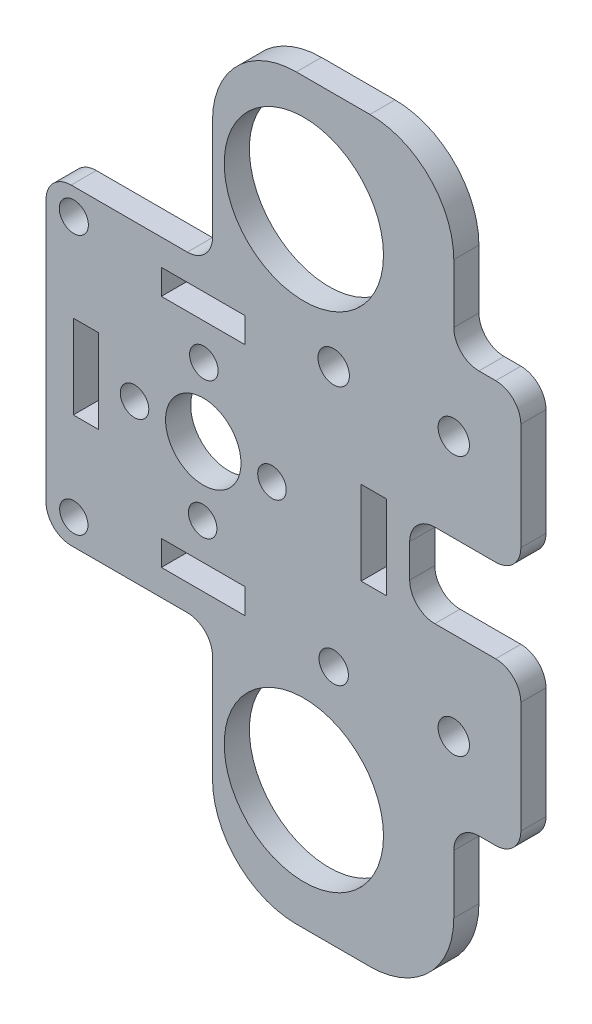
SolidWorks part; units mm, degrees
ref_plane "Front Plane" through (0, 0, 0) normal (0, 0, 1) x (1, 0, 0)
ref_plane "Top Plane" through (0, 0, 0) normal (0, 1, 0) x (1, 0, 0)
ref_plane "Right Plane" through (0, 0, 0) normal (1, 0, 0) x (0, 0, -1)
sketch "Sketch1" plane through (0, 0, 0) normal (0, 0, 1) x (1, 0, 0)
  line L0 (147.062, -92.9701) -> (147.062, -71.8565)
  line L1 (147.062, -92.9701) -> (127.2038, -92.9701)
  line L2 (127.2038, -92.9701) -> (127.2038, -111.5917)
  line L4 (147.062, -151.8871) -> (147.062, -155.8871)
  line L5 (145.9607, -111.5917) -> (157.9607, -111.5917) construction
  line L6 (157.9607, -111.5917) -> (157.9607, -81.5917) construction
  line L7 (157.9607, -111.5917) -> (157.9607, -141.5917) construction
  line L8 (147.062, -71.8565) -> (147.062, -67.8565)
  line L9 (127.2038, -111.5917) -> (127.2038, -130.2155)
  line L10 (127.2038, -130.2155) -> (147.062, -130.2155)
  line L11 (147.062, -130.2155) -> (147.062, -151.8871)
  line L13 (147.062, -67.8565) -> (175.8433, -67.8565)
  line L14 (147.062, -155.8871) -> (175.8433, -155.8871)
  line L15 (175.8433, -67.8565) -> (175.8433, -87.8565)
  line L16 (175.8433, -155.8871) -> (175.8433, -135.8871)
  line L17 (175.8433, -87.8565) -> (183.8433, -87.8565)
  line L18 (175.8433, -135.8871) -> (183.8433, -135.8871)
  line L19 (166.2936, -111.5917) -> (199.239, -111.5917) construction
  line L20 (145.9607, -111.5917) -> (131.9607, -111.5917) construction
  line L21 (145.9607, -111.5917) -> (145.9607, -97.5917) construction
  line L22 (145.9607, -111.5917) -> (145.9607, -125.5917) construction
  line L23 (157.9607, -111.5917) -> (166.2936, -111.5917) construction
  line L24 (130.4607, -106.5917) -> (133.4607, -106.5917)
  line L25 (130.4607, -106.5917) -> (130.4607, -116.5917)
  line L26 (130.4607, -116.5917) -> (133.4607, -116.5917)
  line L27 (133.4607, -106.5917) -> (133.4607, -116.5917)
  line L28 (130.4607, -106.5917) -> (133.4607, -116.5917) construction
  line L29 (130.4607, -116.5917) -> (133.4607, -106.5917) construction
  line L30 (140.9607, -99.0917) -> (150.9607, -99.0917)
  line L31 (140.9607, -99.0917) -> (140.9607, -96.0917)
  line L32 (140.9607, -96.0917) -> (150.9607, -96.0917)
  line L33 (150.9607, -99.0917) -> (150.9607, -96.0917)
  line L34 (140.9607, -99.0917) -> (150.9607, -96.0917) construction
  line L35 (140.9607, -96.0917) -> (150.9607, -99.0917) construction
  line L36 (140.9607, -127.0917) -> (150.9607, -127.0917)
  line L37 (140.9607, -127.0917) -> (140.9607, -124.0917)
  line L38 (140.9607, -124.0917) -> (150.9607, -124.0917)
  line L39 (150.9607, -127.0917) -> (150.9607, -124.0917)
  line L40 (140.9607, -127.0917) -> (150.9607, -124.0917) construction
  line L41 (140.9607, -124.0917) -> (150.9607, -127.0917) construction
  line L42 (185.7907, -111.5917) -> (185.7907, -106.5917) construction
  line L43 (164.7936, -106.5917) -> (167.7936, -106.5917)
  line L44 (164.7936, -106.5917) -> (164.7936, -116.5917)
  line L45 (164.7936, -116.5917) -> (167.7936, -116.5917)
  line L46 (167.7936, -106.5917) -> (167.7936, -116.5917)
  line L47 (164.7936, -106.5917) -> (167.7936, -116.5917) construction
  line L48 (164.7936, -116.5917) -> (167.7936, -106.5917) construction
  line L49 (185.7907, -111.5917) -> (185.7907, -116.5917) construction
  line L50 (183.8433, -87.8565) -> (183.8433, -106.6204)
  line L51 (183.8433, -106.6204) -> (170.5821, -106.6204)
  line L52 (170.5821, -106.6204) -> (170.5821, -116.5917)
  line L53 (170.5821, -116.5917) -> (183.8433, -116.5917)
  line L54 (183.8433, -116.5917) -> (183.8433, -135.8871)
  circle A0 centre (130.52, -96.082) radius 1.7379
  circle A2 centre (161.52, -96.082) radius 1.8732
  circle A3 centre (130.52, -127.1142) radius 1.6901
  circle A4 centre (161.52, -127.082) radius 1.7542
  circle A5 centre (154.1576, -111.6623) radius 1.7
  circle A6 centre (145.8901, -119.7886) radius 1.7
  circle A7 centre (137.7638, -111.5212) radius 1.7
  circle A8 centre (146.0313, -103.3948) radius 1.7
  circle A10 centre (145.9607, -111.5917) radius 4.5
  circle A12 centre (175.8433, -96.1142) radius 1.87
  circle A15 centre (157.9607, -81.5917) radius 9.5
  circle A16 centre (157.9607, -141.5917) radius 9.5
  circle A17 centre (175.8433, -127.1142) radius 1.87
  point P44 (145.9607, -111.5917)
  point P47 (106.5258, -71.8662)
  dimension "D1" = 4
  dimension "D4" = 12
  dimension "D5" = 4
  dimension "D10" = 4
  dimension "D2" = 30
  dimension "D3" = 30
  dimension "D6" = 20
  dimension "D7" = 20
  dimension "D8" = 8
  dimension "D9" = 8
  dimension "D11" = 14
  dimension "D12" = 14
  dimension "D13" = 14
  dimension "D14" = 3
  dimension "D15" = 3
  dimension "D16" = 3
  dimension "D17" = 10
  dimension "D18" = 10
  dimension "D19" = 10
  dimension "D20" = 3
  dimension "D21" = 10
  dimension "D22" = 5
  dimension "D23" = 5
extrude "Boss-Extrude1" add sketch "Sketch1" along normal blind 3
fillet "Fillet1" radius 10 4 edges at (175.8433, -155.8871, 1.5) (147.062, -155.8871, 1.5) (147.062, -67.8565, 1.5) (175.8433, -67.8565, 1.5)
fillet "Fillet2" radius 3 12 edges at (183.8433, -106.6204, 1.5) (183.8433, -116.5917, 1.5) (183.8433, -87.8565, 1.5) (183.8433, -135.8871, 1.5) (175.8433, -135.8871, 1.5) (175.8433, -87.8565, 1.5) (170.5821, -116.5917, 1.5) (170.5821, -106.6204, 1.5) (127.2038, -92.9701, 1.5) (147.062, -92.9701, 1.5) (147.062, -130.2155, 1.5) (127.2038, -130.2155, 1.5)
